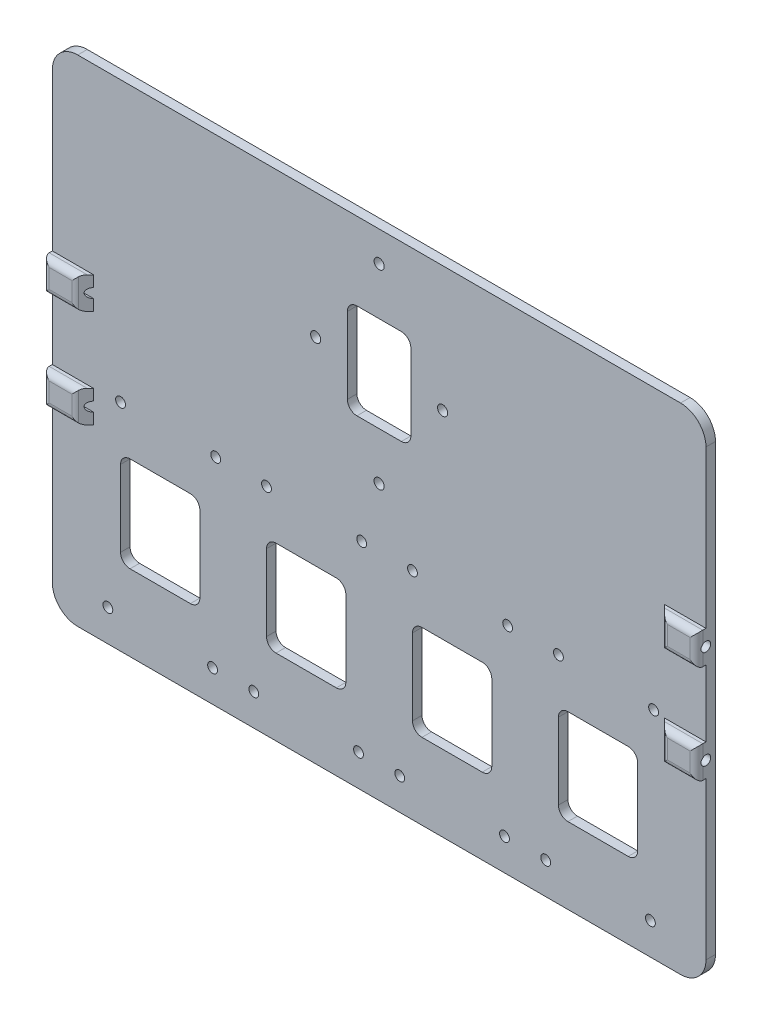
SolidWorks part; units mm, degrees
ref_plane "Front Plane" through (0, 0, 0) normal (1, 0, 0) x (0, 1, 0)
ref_plane "Top Plane" through (0, 0, 0) normal (0, 0, 1) x (0, 1, 0)
ref_plane "Right Plane" through (0, 0, 0) normal (0, 1, 0) x (-1, 0, 0)
sketch "Sketch1" plane through (0, 0, 0) normal (0, 0, 1) x (0, 1, 0)
  line L6 (0, 0) -> (31.4193, 0) construction
  line L7 (-70, -103) -> (70, -103)
  line L8 (-78, -95) -> (-78, 95)
  line L9 (-70, 103) -> (70, 103)
  line L10 (78, -95) -> (78, 95)
  line L11 (-78, -103) -> (78, 103) construction
  line L12 (-78, 103) -> (78, -103) construction
  line L13 (-68, -85.5) -> (-68, -52.5) construction
  line L15 (-10, -86.5) -> (-10, -56.5) construction
  line L23 (38.504, 27.5) -> (38.504, -27.5) construction
  line L25 (-78, 0) -> (-68, 0) construction
  line L30 (68, 0) -> (78, 0) construction
  line L34 (-73, -47.5) -> (-6, -47.5) construction
  line L35 (-73, -47.5) -> (-73, -90.5) construction
  line L40 (-73, -90.5) -> (-6, -90.5) construction
  line L41 (-6, -47.5) -> (-6, -90.5) construction
  line L42 (8.504, 20) -> (68.504, 20) construction
  line L43 (8.504, 20) -> (8.504, -20) construction
  line L44 (8.504, -20) -> (68.504, -20) construction
  line L45 (68.504, 20) -> (68.504, -20) construction
  line L46 (1.004, 27.5) -> (76.004, 27.5) construction
  line L47 (1.004, 27.5) -> (1.004, -27.5) construction
  line L48 (1.004, -27.5) -> (76.004, -27.5) construction
  line L49 (76.004, 27.5) -> (76.004, -27.5) construction
  arc A4 (70, -103) -> (78, -95) centre (70, -95) ccw
  arc A5 (-70, -103) -> (-78, -95) centre (-70, -95) cw
  arc A6 (-78, 95) -> (-70, 103) centre (-70, 95) cw
  arc A7 (70, 103) -> (78, 95) centre (70, 95) cw
  circle A8 centre (-68, -52.5) radius 1.55
  circle A9 centre (-68, -85.5) radius 1.55
  circle A10 centre (-10, -86.5) radius 1.55
  circle A11 centre (-10, -56.5) radius 1.55
  circle A24 centre (-68, -6.5) radius 1.55
  circle A25 centre (-68, -39.5) radius 1.55
  circle A26 centre (-10, -40.5) radius 1.55
  circle A27 centre (-10, -10.5) radius 1.55
  circle A28 centre (-68, 39.5) radius 1.55
  circle A29 centre (-68, 6.5) radius 1.55
  circle A30 centre (-10, 5.5) radius 1.55
  circle A31 centre (-10, 35.5) radius 1.55
  circle A32 centre (-68, 85.5) radius 1.55
  circle A33 centre (-68, 52.5) radius 1.55
  circle A34 centre (-10, 51.5) radius 1.55
  circle A35 centre (-10, 81.5) radius 1.55
  circle A40 centre (8.504, 0) radius 1.6
  circle A41 centre (38.504, 20) radius 1.6
  circle A42 centre (68.504, 0) radius 1.6
  circle A43 centre (38.504, -20) radius 1.6
  point P0 (0, 0)
  point P5 (0, 0)
  dimension "D6" = 8
  dimension "D8" = 3.1
  dimension "D19" = 3.2
  dimension "D1" = 156
  dimension "D3" = 206
  dimension "D7" = 33
  dimension "D10" = 30
  dimension "D5" = 10
  dimension "D4" = 43
  dimension "D11" = 67
  dimension "D12" = 5
  dimension "D13" = 5
  dimension "D9" = 4
  dimension "D15" = 4
  dimension "D16" = 13
  dimension "D17" = 40
  dimension "D18" = 60
  dimension "D21" = 55
  dimension "D22" = 75
  dimension "D20" = 1.996
  dimension "D14" = 4
extrude "Boss-Extrude1" add sketch "Sketch1" along normal blind 3
sketch "Sketch4" plane through (0, 0, 3) normal (0, 0, 1) x (1, 0, 0)
  line L0 (-69, -10) -> (-69, -68) construction
  line L1 (-78.5, -24) -> (-59.5, -24)
  line L2 (-81.5, -27) -> (-81.5, -51)
  line L3 (-78.5, -54) -> (-59.5, -54)
  line L4 (-56.5, -27) -> (-56.5, -51)
  line L5 (-81.5, -10) -> (-51.5, -10) construction
  line L6 (-85.5, -68) -> (-52.5, -68) construction
  line L7 (-81.5, -39) -> (-69, -39) construction
  line L8 (-35.5, -27) -> (-35.5, -51)
  line L9 (-32.5, -24) -> (-13.5, -24)
  line L10 (-32.5, -54) -> (-13.5, -54)
  line L11 (-10.5, -27) -> (-10.5, -51)
  line L12 (10.5, -27) -> (10.5, -51)
  line L13 (13.5, -24) -> (32.5, -24)
  line L14 (13.5, -54) -> (32.5, -54)
  line L15 (35.5, -27) -> (35.5, -51)
  line L16 (56.5, -27) -> (56.5, -51)
  line L17 (59.5, -24) -> (78.5, -24)
  line L18 (59.5, -54) -> (78.5, -54)
  line L19 (81.5, -27) -> (81.5, -51)
  line L20 (69, -8.2965) -> (69, -68) construction
  line L21 (52.5, -68) -> (85.5, -68) construction
  line L22 (-20, 38.504) -> (20, 38.504) construction
  line L23 (-7, 53.504) -> (7, 53.504)
  line L24 (-10, 50.504) -> (-10, 26.504)
  line L25 (-7, 23.504) -> (7, 23.504)
  line L26 (10, 50.504) -> (10, 26.504)
  line L27 (0, 68.504) -> (0, 8.504) construction
  arc A0 (78.5, -54) -> (81.5, -51) centre (78.5, -51) ccw
  arc A1 (78.5, -24) -> (81.5, -27) centre (78.5, -27) cw
  arc A2 (56.5, -27) -> (59.5, -24) centre (59.5, -27) cw
  arc A3 (56.5, -51) -> (59.5, -54) centre (59.5, -51) ccw
  arc A4 (32.5, -24) -> (35.5, -27) centre (32.5, -27) cw
  arc A5 (32.5, -54) -> (35.5, -51) centre (32.5, -51) ccw
  arc A6 (10.5, -51) -> (13.5, -54) centre (13.5, -51) ccw
  arc A7 (10.5, -27) -> (13.5, -24) centre (13.5, -27) cw
  arc A8 (-13.5, -54) -> (-10.5, -51) centre (-13.5, -51) ccw
  arc A9 (-13.5, -24) -> (-10.5, -27) centre (-13.5, -27) cw
  arc A10 (-35.5, -27) -> (-32.5, -24) centre (-32.5, -27) cw
  arc A11 (-35.5, -51) -> (-32.5, -54) centre (-32.5, -51) ccw
  arc A12 (-59.5, -54) -> (-56.5, -51) centre (-59.5, -51) ccw
  arc A13 (-81.5, -51) -> (-78.5, -54) centre (-78.5, -51) ccw
  arc A14 (-59.5, -24) -> (-56.5, -27) centre (-59.5, -27) cw
  arc A15 (-78.5, -24) -> (-81.5, -27) centre (-78.5, -27) ccw
  arc A16 (-10, 26.504) -> (-7, 23.504) centre (-7, 26.504) ccw
  arc A17 (7, 23.504) -> (10, 26.504) centre (7, 26.504) ccw
  arc A18 (7, 53.504) -> (10, 50.504) centre (7, 50.504) cw
  arc A19 (-7, 53.504) -> (-10, 50.504) centre (-7, 50.504) ccw
  point P5 (-58.5, -8.5)
  point P11 (-58.5, -8.5)
  point P67 (-56.5, -54)
  point P72 (-56.5, -24)
  point P75 (-81.5, -24)
  point P98 (10, 23.504)
  point P101 (10, 53.504)
  point P104 (-10, 53.504)
  dimension "D4" = 3
  dimension "D7" = 3
  dimension "D1" = 25
  dimension "D2" = 30
  dimension "D3" = 4
  dimension "D5" = 20
  dimension "D6" = 30
extrude "Cut-Extrude3" cut sketch "Sketch4" against normal up to next
sketch "Sketch3" plane through (103, 0, 0) normal (1, 0, 0) x (0, 1, 0)
  line L0 (0, 3) -> (0, 0) construction
  line L1 (-70, 3) -> (70, 3) construction
  line L2 (-70, 0) -> (70, 0) construction
  line L3 (-20.5, 3) -> (-10.5, 3) construction
  line L7 (-20.5, 6) -> (-10.5, 6)
  line L8 (-20.5, 6) -> (-20.5, 0)
  line L9 (-20.5, 0) -> (-10.5, 0)
  line L10 (-10.5, 6) -> (-10.5, 0)
  line L11 (10.5, 6) -> (20.5, 6)
  line L12 (10.5, 6) -> (10.5, 0)
  line L13 (10.5, 0) -> (20.5, 0)
  line L14 (20.5, 6) -> (20.5, 0)
  circle A1 centre (-15.5, 3) radius 1.5
  circle A2 centre (15.5, 3) radius 1.5
  point P12 (0, 0)
  point P13 (-9.3777, 1.7532)
  point P15 (-19.3777, 3)
  point P16 (-19.831, 3)
  point P24 (0, 0)
  point P25 (0, 0)
  point P26 (0, 0)
  point P27 (15.5, 3)
  dimension "D1" = 3
  dimension "D2" = 3
  dimension "D3" = 31
  dimension "D4" = 10
  dimension "D5" = 6
extrude "Boss-Extrude2" add sketch "Sketch3" against normal blind 10 contours L7 L10 L9 L8 | L11 L14 L13 L12
extrude "Boss-Extrude3" add sketch "Sketch3<4>" along normal blind 10 from surface contours L10 L9 L8 L7 | L12 L13 L14 L11 starting at face at (-103, 0, 1.5)
sketch "Sketch3<4>" plane through (103, 0, 0) normal (1, 0, 0) x (0, 1, 0) same geometry as "Sketch3"
extrude "Cut-Extrude4" cut sketch "Sketch3<6>" against normal blind 10 contours A1 | A2
sketch "Sketch3<6>" plane through (103, 0, 0) normal (1, 0, 0) x (0, 1, 0) same geometry as "Sketch3"
extrude "Cut-Extrude5" cut sketch "Sketch3<7>" along normal blind 10 from surface contours A2 | A1 starting at face at (-103, 0, 3.5)
sketch "Sketch3<7>" plane through (103, 0, 0) normal (1, 0, 0) x (0, 1, 0) same geometry as "Sketch3"
chamfer "Chamfer1" distance 3 angle 45 4 edges at (93, -18.75, 3) (93, 12.25, 3) (-93, -18.75, 3) (-93, 12.25, 3)
fillet "Fillet1" radius 2 16 edges at (93, -15.5, 6) (98, -10.5, 6) (103, -15.5, 6) (93, 15.5, 6) (98, 20.5, 6) (103, 15.5, 6) (-98, -10.5, 6) (-93, -15.5, 6) (-98, -20.5, 6) (-103, -15.5, 6) (-98, 20.5, 6) (-93, 15.5, 6) (-98, 10.5, 6) (-103, 15.5, 6) (98, -20.5, 6) (98, 10.5, 6)
equation "\"MotorDriverLength\"= 60mm"
equation "\"MotorLength\"= 60"
equation "\"MotorDriverWidth\"=44"
equation "\"MotorWidth\"= 37"
equation "\"InnerWallThickness\"=3"
equation "\"BatteryWidth\"= 60"
equation "\"OuterWallThickness\" = 6"
equation "\"CompartmentHeight\"=37"
equation "\"CompartmentWidth\"= \"MotorDriverLength\""
equation "\"MotorDiameter\"=37"
equation "\"BatteryHeight\"=24.2019"
equation "\"MotorDriverHeight\"=28"
equation "\"CircuitHeight\"=30"
equation "\"FanThickness\"= 10"
equation "\"FanHeight\"=50"
equation "\"MotorShaftHole\"=12"
equation "\"BearingBore\"=4"
equation "\"MinShinWidth\"= 20"
equation "\"ShinThickness\"=10"
equation "\"PivotDistance\"=30"
equation "\"ThighLength\"= 200"
equation "\"KneeLength\" =20"
equation "\"HipBore\"=27"
equation "\"ThighThickness\"=20"
equation "\"MaxBending\"=135"
equation "\"MaxStretchingAngle\"= 140"
equation "\"ThighJointDistance\"=157.485"
equation "\"ShinLength\"=120"
equation "\"BearingDiameter\"= 10"
equation "\"CircuitLength\"=50"
equation "\"ChessisInnerWidth\"= \"OuterWallThickness\" * 2 + \"MotorDriverLength\" + \"MotorDiameter\" + \"InnerWallThickness\" * 3 + \"CircuitLength\""
equation "\"ChessisHeight\"= \"BatteryHeight\" + 10 + \"InnerWallThickness\" + \"MotorDiameter\" + 10 + \"OuterWallThickness\" * 2"
equation "\"ChassisWidth\"= \"MotorDriverWidth\"*4+30"
equation "\"D3@Sketch1\"=\"ChassisWidth\""
equation "\"D1@Sketch1\"=\"ChessisInnerWidth\"-\"OuterWallThickness\"*2"
